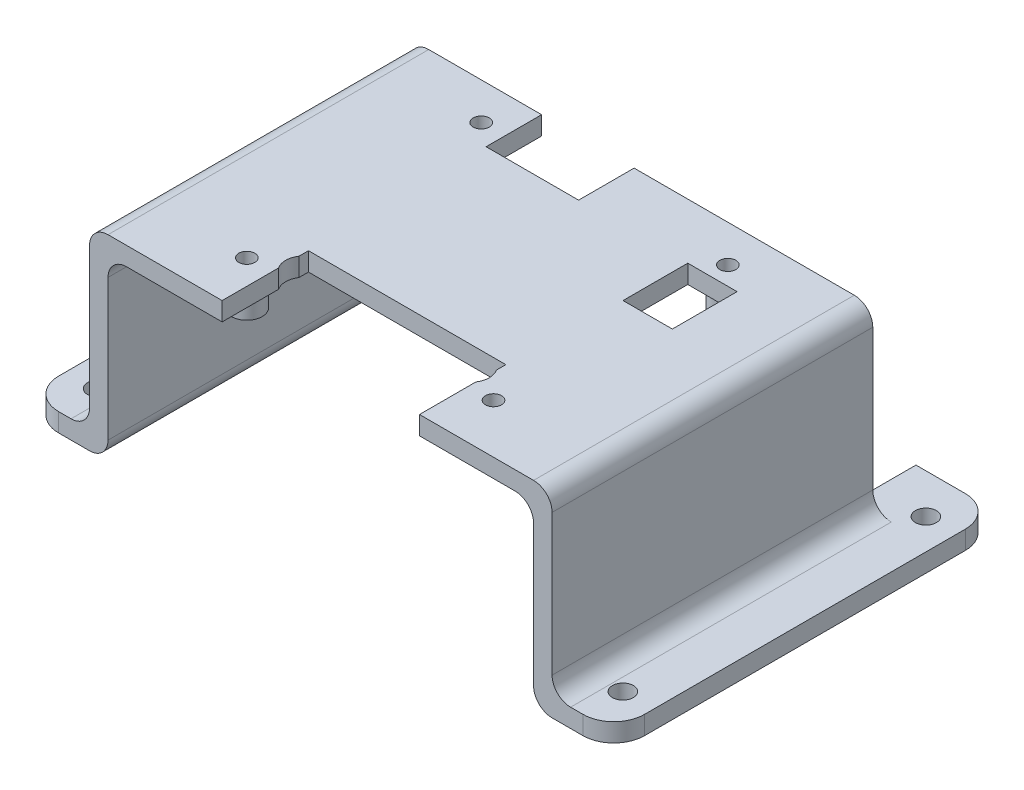
SolidWorks part; units mm, degrees
ref_plane "Front Plane" through (0, 0, 0) normal (0, 0, 1) x (1, 0, 0)
ref_plane "Top Plane" through (0, 0, 0) normal (0, 1, 0) x (1, 0, 0)
ref_plane "Right Plane" through (0, 0, 0) normal (1, 0, 0) x (0, 0, -1)
sketch "Sketch1" plane through (0, 0, 0) normal (0, 1, 0) x (1, 0, 0)
  line L0 (90.0435, 55.565) -> (90.0435, 6.435) construction
  line L1 (0, 0) -> (95, 0)
  line L2 (0, 0) -> (0, 62)
  line L3 (0, 62) -> (95, 62)
  line L4 (95, 0) -> (95, 62)
  line L5 (4.9565, 55.565) -> (4.9565, 6.435) construction
  line L6 (4.9565, 55.565) -> (90.0435, 55.565) construction
  circle A0 centre (90.0435, 55.565) radius 1.7
  circle A1 centre (90.0435, 6.435) radius 1.7
  circle A2 centre (4.9565, 55.565) radius 1.7
  circle A3 centre (4.9565, 6.435) radius 1.7
  point P9 (0, 31)
  point P10 (90.0435, 31)
  point P15 (4.9565, 31)
  point P16 (95, 31)
  point P17 (47.5, 55.565)
  point P18 (47.5, 62)
  dimension "D3" = 3.4
  dimension "D4" = 3.4
  dimension "D5" = 49.13
  dimension "D6" = 3.4
  dimension "D7" = 3.4
  dimension "D1" = 62
  dimension "D2" = 95
  dimension "D8" = 49.13
  dimension "D9" = 85.087
extrude "Boss-Extrude1" add sketch "Sketch1" along normal blind 3
sketch "Sketch2" plane through (0, 3, 0) normal (0, 1, 0) x (1, 0, 0)
  line L0 (4.9565, 55.565) -> (90.0435, 55.565) construction
  line L1 (10, 52) -> (85, 52)
  line L2 (10, 52) -> (10, 0)
  line L3 (10, 0) -> (85, 0)
  line L4 (85, 52) -> (85, 0)
  line L5 (4.9565, 6.435) -> (90.0435, 6.435) construction
  line L6 (95, 62) -> (0, 62) construction
  line L7 (0, 0) -> (95, 0) construction
  point P15 (47.5, 62)
  point P16 (47.5, 52)
  dimension "D1" = 75
  dimension "D2" = 10
  dimension "D3" = 0
extrude "Boss-Extrude2" add sketch "Sketch2" along normal blind 28.85
sketch "Sketch3" plane through (0, 0, 0) normal (0, 0, 1) x (1, 0, 0)
  line L0 (10, 31.85) -> (85, 31.85) construction
  line L1 (13, 28.85) -> (82, 28.85)
  line L2 (13, 28.85) -> (13, 3)
  line L3 (13, 3) -> (82, 3)
  line L4 (82, 28.85) -> (82, 3)
  line L5 (10, 31.85) -> (10, 3) construction
  line L6 (85, 31.85) -> (85, 3) construction
  line L7 (10, 3) -> (0, 3) construction
  dimension "D1" = 3
  dimension "D2" = 3
  dimension "D3" = 3
extrude "Cut-Extrude1" cut sketch "Sketch3" against normal through all
sketch "Sketch4" plane through (0, 0, 0) normal (0, 0, 1) x (1, 0, 0)
  line L0 (0, 0) -> (95, 0) construction
  line L1 (13, 3) -> (82, 3)
  line L2 (13, 3) -> (13, 0)
  line L3 (13, 0) -> (82, 0)
  line L4 (82, 3) -> (82, 0)
extrude "Cut-Extrude2" cut sketch "Sketch4" against normal through all
sketch "Sketch5" plane through (0, 31.85, 0) normal (0, 1, 0) x (1, 0, 0)
  line L0 (85, 52) -> (10, 52) construction
  line L1 (27.5, 46) -> (67.5, 46) construction
  line L2 (27.5, 46) -> (27.5, 8) construction
  line L3 (27.5, 8) -> (67.5, 8) construction
  line L4 (67.5, 46) -> (67.5, 8) construction
  line L6 (47.5, 46) -> (47.5, 8) construction
  line L7 (10, 0) -> (85, 0) construction
  line L8 (63.5, 0) -> (31.5, 0)
  line L9 (63.5, 0) -> (63.5, 14)
  line L10 (63.5, 14) -> (31.5, 14)
  line L11 (31.5, 0) -> (31.5, 14)
  circle A0 centre (27.5, 46) radius 1.3
  circle A1 centre (27.5, 8) radius 1.3
  circle A2 centre (67.5, 8) radius 1.3
  circle A3 centre (67.5, 46) radius 1.3
  point P6 (47.5, 52)
  point P7 (47.5, 46)
  point P24 (47.5, 14)
  dimension "D3" = 2.6
  dimension "D4" = 2.6
  dimension "D1" = 40
  dimension "D2" = 38
  dimension "D5" = 14
  dimension "D6" = 32
  dimension "5" = 8
extrude "Cut-Extrude3" cut sketch "Sketch5" against normal through all
sketch "Sketch7" plane through (0, 31.85, 0) normal (0, 1, 0) x (1, 0, 0)
  line L2 (47.5, 14) -> (47.5, 3.8387) construction
  line L3 (63.5, 14) -> (31.5, 14) construction
  circle A0 centre (34, 10.8) radius 3
  circle A5 centre (61, 10.8) radius 3
  circle A6 centre (27.5, 8) radius 1.3 construction
  dimension "D1" = 6
  dimension "D2" = 2.8
extrude "Cut-Extrude5" cut sketch "Sketch7" against normal through all
sketch "Sketch6" plane through (0, 31.85, 0) normal (0, 1, 0) x (1, 0, 0)
  line L0 (85, 52) -> (10, 52) construction
  line L1 (31.3, 52) -> (46.3, 52)
  line L2 (31.3, 52) -> (31.3, 43)
  line L3 (31.3, 43) -> (46.3, 43)
  line L4 (46.3, 52) -> (46.3, 43)
  line L5 (85, 0) -> (85, 52) construction
  line L6 (64, 43) -> (72, 43)
  line L7 (64, 43) -> (64, 32.5)
  line L8 (64, 32.5) -> (72, 32.5)
  line L9 (72, 43) -> (72, 32.5)
  circle A0 centre (67.5, 46) radius 1.3 construction
  circle A1 centre (27.5, 46) radius 1.3 construction
  point P12 (67.5, 46)
  point P13 (68, 43)
  dimension "D1" = 3
  dimension "D2" = 8
  dimension "D3" = 9
  dimension "D4" = 15
  dimension "D5" = 3.8
  dimension "D6" = 10.5
  dimension "D7" = 17
extrude "Cut-Extrude4" cut sketch "Sketch6" against normal through all
fillet "Fillet1" radius 3 8 edges at (13, 0, -31) (82, 0, -31) (10, 3, -26) (85, 3, -26) (10, 31.85, -26) (85, 31.85, -26) (13, 28.85, -26) (82, 28.85, -26)
sketch "Sketch8" plane through (0, 28.85, 0) normal (0, -1, 0) x (1, 0, 0)
  circle A0 centre (27.5, -8) radius 1.3
  circle A1 centre (27.5, -8) radius 2.5
  circle A2 centre (67.5, -8) radius 1.3
  circle A3 centre (67.5, -8) radius 2.5
  circle A4 centre (67.5, -8) radius 1.3 construction
  circle A5 centre (27.5, -46) radius 1.3
  circle A6 centre (27.5, -46) radius 2.5
  circle A7 centre (27.5, -46) radius 1.3 construction
  circle A8 centre (67.5, -46) radius 1.3
  circle A9 centre (67.5, -46) radius 2.5
  circle A10 centre (67.5, -46) radius 1.3 construction
  point P7 (0, 0)
  dimension "D1" = 5
  dimension "D2" = 2.6
  dimension "D3" = 5
  dimension "D4" = 2.6
  dimension "D5" = 5
  dimension "D6" = 2.6
  dimension "D7" = 5
  dimension "D8" = 2.6
extrude "Boss-Extrude4" add sketch "Sketch8" along normal blind 4
fillet "Fillet2" radius 5 4 edges at (95, 1.5, -62) (95, 1.5, 0) (0, 1.5, 0) (0, 1.5, -62)
